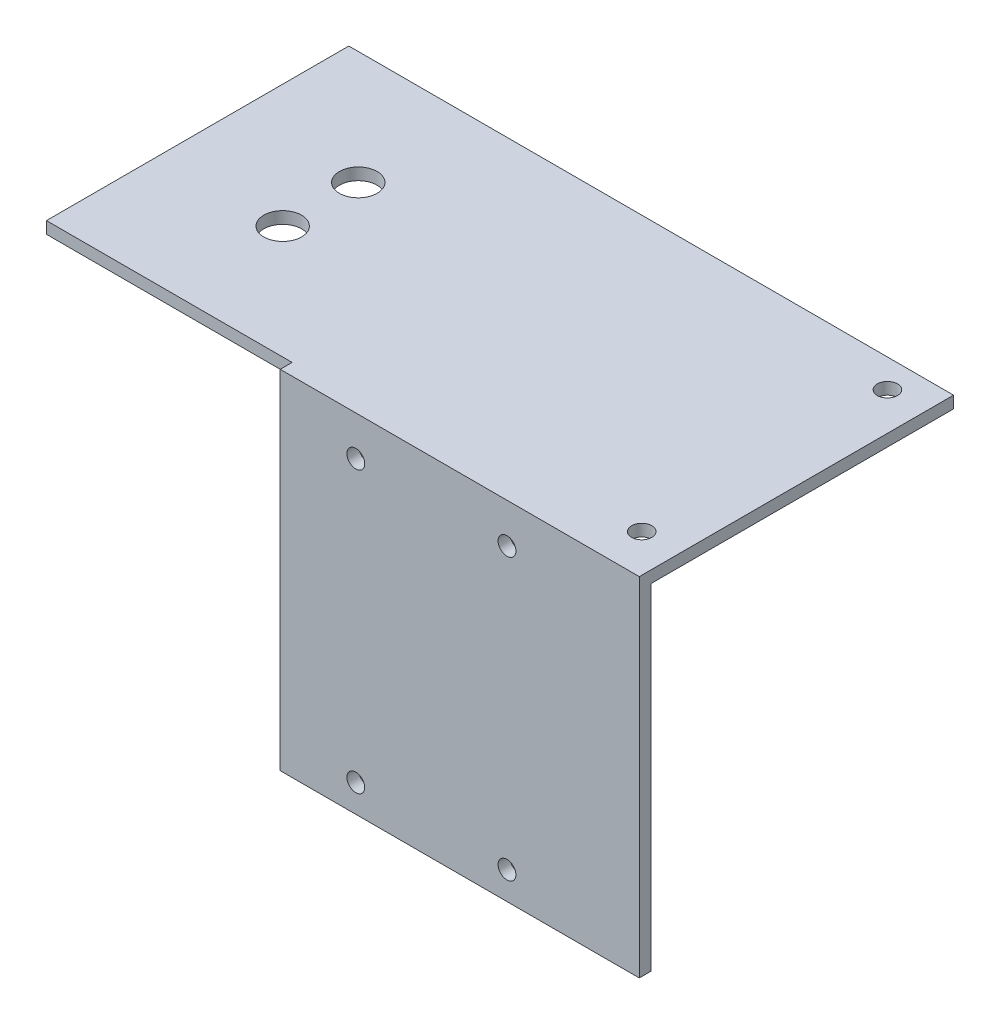
SolidWorks part; units mm, degrees
ref_plane "Front Plane" through (0, 0, 0) normal (0, 0, 1) x (1, 0, 0)
ref_plane "Top Plane" through (0, 0, 0) normal (0, 1, 0) x (1, 0, 0)
ref_plane "Right Plane" through (0, 0, 0) normal (1, 0, 0) x (0, 0, -1)
sketch "Sketch1" plane through (0, 0, 0) normal (0, 0, 1) x (1, 0, 0)
  line L0 (38.1, 51.75) -> (12.7, 51.75) construction
  line L1 (0, 58.4) -> (60.325, 58.4)
  line L2 (0, 58.4) -> (0, 0)
  line L3 (0, 0) -> (60.325, 0)
  line L4 (60.325, 58.4) -> (60.325, 0)
  line L6 (12.7, 51.75) -> (12.7, 4.65) construction
  line L8 (12.7, 4.65) -> (38.1, 4.65) construction
  line L9 (38.1, 51.75) -> (38.1, 4.65) construction
  circle A4 centre (12.7, 51.75) radius 1.5
  circle A5 centre (38.1, 51.75) radius 1.5
  circle A6 centre (12.7, 4.65) radius 1.5
  circle A7 centre (38.1, 4.65) radius 1.5
  dimension "D3" = 3
  dimension "D1" = 58.4
  dimension "D2" = 60.325
  dimension "D4" = 47.1
  dimension "D6" = 4.65
  dimension "D7" = 25.4
  dimension "D9" = 12.7
extrude "Boss-Extrude1" add sketch "Sketch1" against normal blind 2
sketch "Sketch2" plane through (0, 0, -2) normal (0, 0, -1) x (-1, 0, 0)
  line L0 (0, 56.4) -> (41.275, 56.4)
  line L1 (0, 58.4) -> (0, 0) construction
  line L2 (0, 56.4) -> (-60.325, 56.4)
  line L3 (-60.325, 56.4) -> (-60.325, 58.4)
  line L4 (-60.325, 58.4) -> (0, 58.4) construction
  line L5 (-60.325, 58.4) -> (0, 58.4)
  line L6 (41.275, 56.4) -> (41.275, 58.4)
  line L7 (41.275, 58.4) -> (0, 58.4)
  dimension "D1" = 60.325
  dimension "D2" = 41.275
  dimension "D3" = 2
extrude "Boss-Extrude2" add sketch "Sketch2" along normal blind 50.8
sketch "Sketch3" plane through (0, 58.4, 0) normal (0, 1, 0) x (1, 0, 0)
  line L0 (53.975, 48.0375) -> (53.975, 6.7625) construction
  line L1 (-41.275, 52.8) -> (60.325, 52.8) construction
  line L2 (60.325, 52.8) -> (60.325, 0) construction
  line L3 (-20.6375, 33.75) -> (-20.6375, 21.05) construction
  line L4 (-41.275, 52.8) -> (-41.275, 2) construction
  circle A0 centre (53.975, 48.0375) radius 1.7
  circle A1 centre (53.975, 6.7625) radius 1.7
  circle A2 centre (-20.6375, 33.75) radius 3.175
  circle A3 centre (-20.6375, 21.05) radius 3.175
  point P10 (-20.6375, 27.4)
  point P13 (-41.275, 27.4)
  dimension "D1" = 3.4
  dimension "D2" = 41.275
  dimension "D6" = 6.35
  dimension "D7" = 6.35
  dimension "D3" = 4.7625
  dimension "D4" = 6.35
  dimension "D5" = 12.7
  dimension "D8" = 20.6375
extrude "Cut-Extrude1" cut sketch "Sketch3" against normal through all
